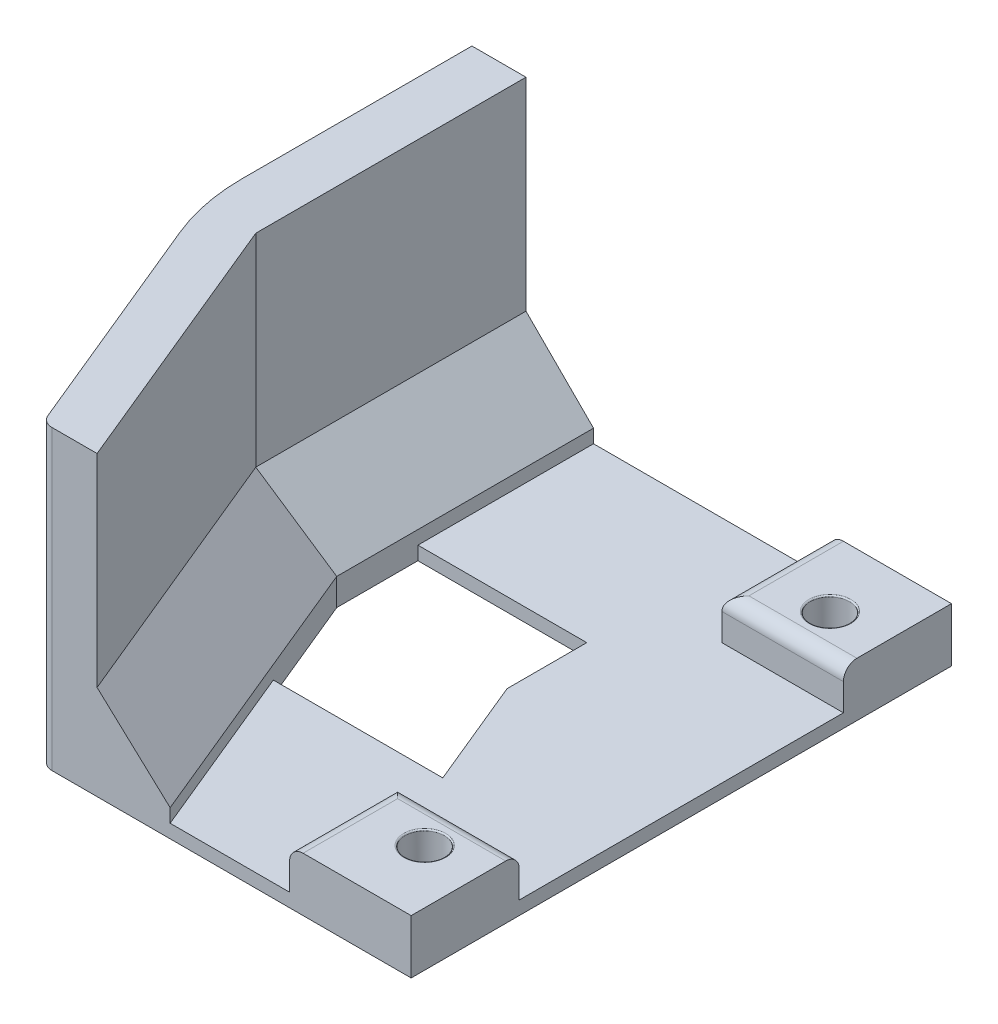
SolidWorks part; units mm, degrees
ref_plane "前视基准面" through (0, 0, 0) normal (0, 0, 1) x (1, 0, 0)
ref_plane "上视基准面" through (0, 0, 0) normal (0, 1, 0) x (1, 0, 0)
ref_plane "右视基准面" through (0, 0, 0) normal (1, 0, 0) x (0, 0, -1)
other "Configuration Table"
sketch "草图1" plane through (0, 0, 0) normal (0, 1, 0) x (1, 0, 0)
  line L1 (0, 0) -> (-53, 0)
  line L2 (0, 0) -> (0, 80)
  line L3 (0, 80) -> (-53, 80)
  line L4 (-53, 0) -> (-53, 80)
  dimension "D1" = 80
  dimension "D2" = 53
extrude "凸台-拉伸1" add sketch "草图1" along normal blind 4
sketch "草图2" plane through (0, 4, 0) normal (0, 1, 0) x (1, 0, 0)
  line L0 (-45, 40) -> (-28.5, 0)
  line L1 (-53, 80) -> (-45, 80)
  line L2 (-53, 80) -> (-53, 40)
  line L4 (-45, 80) -> (-45, 40)
  line L5 (-53, 0) -> (0, 0) construction
  line L6 (-28.5, 0) -> (-36.5, 0)
  line L7 (-36.5, 0) -> (-53, 40)
  dimension "D1" = 8
  dimension "D2" = 40
  dimension "D3" = 8
  dimension "D4" = 16.5
extrude "凸台-拉伸2" add sketch "草图2" along normal blind 40
sketch "草图3" plane through (0, 4, 0) normal (0, 1, 0) x (1, 0, 0)
  line L3 (-36.5, 0) -> (-53, 40)
  line L4 (-53, 40) -> (-53, 0)
  line L5 (-53, 0) -> (-36.5, 0)
  line L6 (-36.5, 0) -> (-53, 40)
  line L7 (-53, 40) -> (-53, 0)
  line L8 (-53, 0) -> (-36.5, 0)
  dimension "D1" = 0
extrude "切除-拉伸1" cut sketch "草图3" against normal blind 16
sketch "草图4" plane through (0, 0, 0) normal (1, 0, 0) x (0, 0, -1)
  line L4 (0, 0) -> (80, 0)
  line L5 (80, 0) -> (80, 4)
  line L6 (80, 4) -> (0, 4)
  line L7 (0, 4) -> (0, 0)
  line L8 (0, 0) -> (80, 0)
  line L9 (80, 0) -> (80, 4)
  line L10 (80, 4) -> (0, 4)
  line L11 (0, 4) -> (0, 0)
  dimension "D1" = 0
extrude "凸台-拉伸3" add sketch "草图4" along normal blind 20
sketch "草图7" plane through (0, 4, 0) normal (0, 1, 0) x (1, 0, 0)
  line L0 (-28.5, 0) -> (20, 0) construction
  line L1 (20, 80) -> (0, 80)
  line L2 (20, 80) -> (20, 0)
  line L3 (20, 0) -> (0, 0)
  line L4 (0, 80) -> (0, 0)
  dimension "D1" = 20
extrude "凸台-拉伸4" add sketch "草图7" along normal blind 4
sketch "草图5" plane through (0, 4, 0) normal (0, 1, 0) x (1, 0, 0)
  line L0 (20, 40) -> (-21.588, 40) construction
  line L1 (20, 80) -> (20, 0) construction
  line L2 (20, 80) -> (10, 80) construction
  line L3 (0, 80) -> (-45, 80) construction
  line L4 (10, 80) -> (10, 70) construction
  circle A0 centre (10, 70) radius 1.45
  circle A1 centre (10, 10) radius 1.45
  dimension "D3" = 2.9
  dimension "D1" = 10
  dimension "D2" = 10
extrude "切除-拉伸2" cut sketch "草图5" against normal blind 4 and the other way blind 4
sketch "草图8" plane through (0, 8, 0) normal (0, 1, 0) x (1, 0, 0)
  circle A0 centre (10, 70) radius 2.9
  circle A1 centre (10, 10) radius 2.9
  dimension "D1" = 5.8
  dimension "D2" = 5.8
extrude "切除-拉伸3" cut sketch "草图8" against normal blind 6
sketch "草图9" plane through (20, 0, 0) normal (1, 0, 0) x (0, 0, -1)
  line L4 (0, 8) -> (0, 0)
  line L5 (0, 0) -> (80, 0)
  line L6 (80, 0) -> (80, 8)
  line L7 (80, 8) -> (0, 8)
  line L8 (0, 8) -> (0, 0)
  line L9 (0, 0) -> (80, 0)
  line L10 (80, 0) -> (80, 8)
  line L11 (80, 8) -> (0, 8)
  dimension "D1" = 0
extrude "切除-拉伸4" cut sketch "草图9" against normal blind 2
sketch "草图10" plane through (0, 8, 0) normal (0, 1, 0) x (1, 0, 0)
  line L0 (0, 80) -> (0, 0) construction
  line L1 (0, 64) -> (18, 64)
  line L2 (0, 64) -> (0, 16)
  line L3 (0, 16) -> (18, 16)
  line L4 (18, 64) -> (18, 16)
  line L5 (18, 80) -> (18, 0) construction
  line L6 (18, 80) -> (0, 80) construction
  line L7 (0, 0) -> (18, 0) construction
  dimension "D1" = 16
  dimension "D2" = 16
extrude "切除-拉伸5" cut sketch "草图10" against normal up to surface (4 mm away) up to face at (-23.7, 4, -40)
sketch "草图11" plane through (0, 4, 0) normal (0, 1, 0) x (1, 0, 0)
  line L0 (-35, 41.9815) -> (-28.4076, 26)
  line L2 (-35, 41.9815) -> (-35, 54)
  line L3 (-35, 54) -> (-10, 54)
  line L4 (-10, 42.2005) -> (-10, 54)
  line L5 (-28.4076, 26) -> (-3.3173, 26)
  line L6 (-3.3173, 26) -> (-10, 42.2005)
  line L7 (-28.5, 0) -> (-45, 40) construction
  line L8 (0, 80) -> (0, 64) construction
  line L10 (-45, 40) -> (-45, 80) construction
  line L11 (18, 16) -> (0, 16) construction
  line L13 (0, 64) -> (18, 64) construction
  dimension "D1" = 10
  dimension "D2" = 10
  dimension "D3" = 10
  dimension "D4" = 10
  dimension "D5" = 10
extrude "切除-拉伸6" cut sketch "草图11" against normal up to surface (4 mm away) up to face at (10, 0, -11.45)
chamfer "倒角1" distance 10 angle 45 2 edges at (-36.75, 4, -20) (-45, 4, -60)
fillet "圆角1" radius 30 1 edges at (-53, 22, -40)
fillet "圆角2" radius 2 5 edges at (0, 8, -8) (9, 8, -16) (0, 8, -72) (9, 8, -64) (-36.5, 22, 0)
fillet "圆角3" radius 0.2 4 edges at (10, 2, -68.55) (10, 8, -67.1) (10, 2, -8.55) (10, 8, -7.1)
sketch "草图12" plane through (0, 4, 0) normal (0, 1, 0) x (1, 0, 0)
  line L13 (-3.3173, 26) -> (-28.4076, 26)
  line L14 (-28.4076, 26) -> (-17.6826, 0)
  line L15 (-17.6826, 0) -> (0, 0)
  line L16 (0, 0) -> (0, 16)
  line L17 (0, 16) -> (18, 16)
  line L18 (18, 16) -> (18, 64)
  line L19 (18, 64) -> (0, 64)
  line L20 (0, 64) -> (0, 80)
  line L21 (0, 80) -> (-35, 80)
  line L22 (-35, 80) -> (-35, 54)
  line L23 (-35, 54) -> (-10, 54)
  line L24 (-10, 54) -> (-10, 42.2005)
  line L25 (-10, 42.2005) -> (-3.3173, 26)
  line L26 (-3.3173, 26) -> (-28.4076, 26)
  line L27 (-28.4076, 26) -> (-17.6826, 0)
  line L28 (-17.6826, 0) -> (0, 0)
  line L29 (0, 0) -> (0, 16)
  line L30 (0, 16) -> (18, 16)
  line L31 (18, 16) -> (18, 64)
  line L32 (18, 64) -> (0, 64)
  line L33 (0, 64) -> (0, 80)
  line L34 (0, 80) -> (-35, 80)
  line L35 (-35, 80) -> (-35, 54)
  line L36 (-35, 54) -> (-10, 54)
  line L37 (-10, 54) -> (-10, 42.2005)
  line L38 (-10, 42.2005) -> (-3.3173, 26)
  dimension "D1" = 0
extrude "切除-拉伸7" cut sketch "草图12" against normal blind 2
